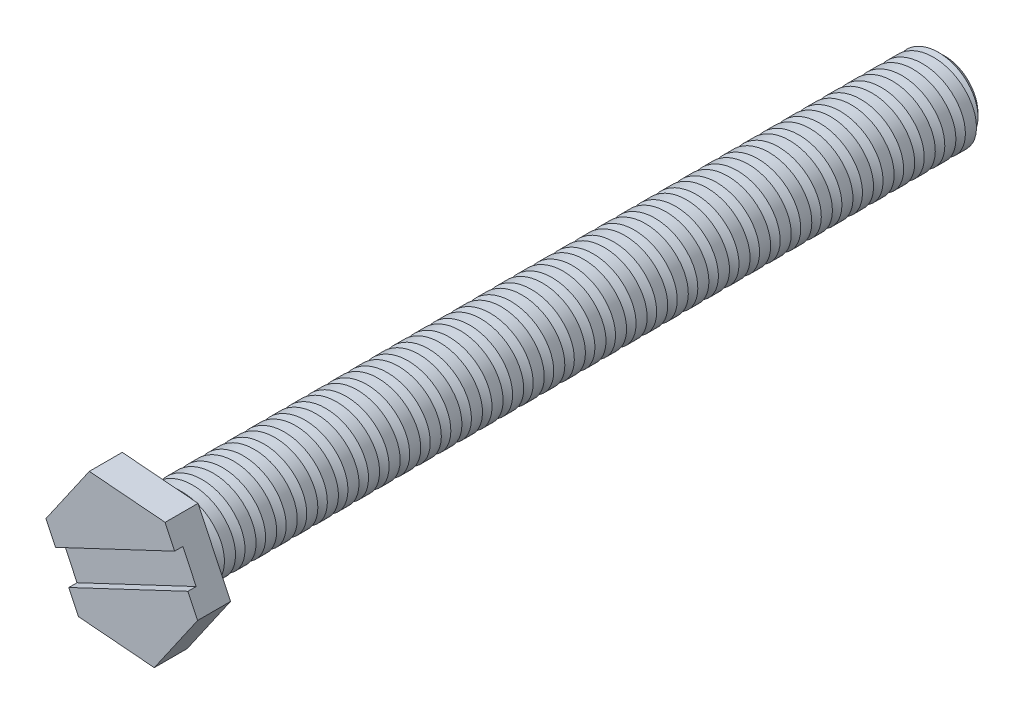
SolidWorks part; units mm, degrees
ref_plane "Plano frontal" through (0, 0, 0) normal (0, 0, 1) x (1, 0, 0)
ref_plane "Plano superior" through (0, 0, 0) normal (0, 1, 0) x (1, 0, 0)
ref_plane "Plano direito" through (0, 0, 0) normal (1, 0, 0) x (0, 0, -1)
sketch "Esboço1" plane through (0, 0, 0) normal (0, 0, 1) x (1, 0, 0)
  circle A0 centre (0, 0) radius 2.5
  dimension "D1" = 5
extrude "Ressalto-extrusão1" add sketch "Esboço1" along normal blind 48
sketch "Esboço2" plane through (0, 0, 48) normal (0, 0, 1) x (1, 0, 0)
  line L1 (4.6031, -0.3806) -> (2.6311, 3.7961)
  line L2 (2.6311, 3.7961) -> (-1.972, 4.1767)
  line L3 (-1.972, 4.1767) -> (-4.6031, 0.3806)
  line L4 (-4.6031, 0.3806) -> (-2.6311, -3.7961)
  line L5 (-2.6311, -3.7961) -> (1.972, -4.1767)
  line L6 (1.972, -4.1767) -> (4.6031, -0.3806)
  circle A0 centre (0, 0) radius 4 construction
  dimension "D1" = 8
extrude "Ressalto-extrusão2" add sketch "Esboço2" along normal blind 2
sketch "Esboço3" plane through (0, 0, 50) normal (0, 0, 1) x (1, 0, 0)
  line L0 (-4.024, -0.8459) -> (3.2102, 2.5696)
  line L1 (-4.6031, 0.3806) -> (-2.6311, -3.7961) construction
  line L2 (4.6031, -0.3806) -> (2.6311, 3.7961) construction
  line L3 (3.2102, 2.5696) -> (4.0165, 0.8618)
  line L4 (4.0165, 0.8618) -> (-3.2177, -2.5537)
  line L5 (-3.2177, -2.5537) -> (-4.024, -0.8459)
extrude "Corte-extrusão1" cut sketch "Esboço3" against normal blind 0.5
chamfer "Chanfro1" distance 0.5 angle 45 1 edges at (2.5, 0, 0)
sketch "Esboço5" plane through (0, 0, 0) normal (0, 0, -1) x (-1, 0, 0)
  circle A0 centre (0, 0) radius 2
curve "Hélice/Espiral1" pitch 1.25 height 47.5 radius 2 centre (0, 0, 0) axis (0, 0, 1) start towards (-1, 0, 0)
sketch "Esboço6" plane through (0, 0, 0) normal (1, 0, 0) x (0, 0, -1)
  line L1 (0, -2) -> (-0.8227, -3.425)
  line L2 (-0.8227, -3.425) -> (0.8227, -3.425)
  line L3 (0.8227, -3.425) -> (0, -2)
  circle A0 centre (0, -2.95) radius 0.475 construction
  dimension "D1" = 0.95
sweep "Varredura de corte1" cut profiles "Esboço6" path "Hélice/Espiral1"
